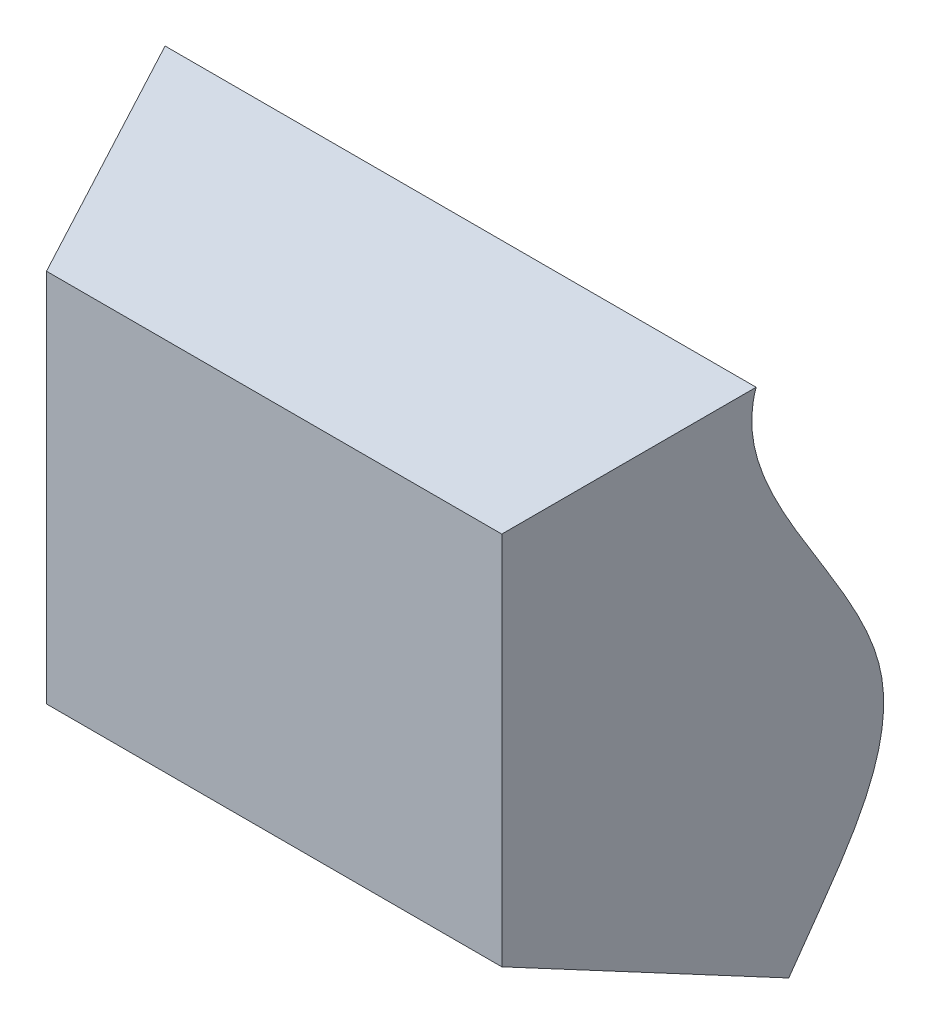
SolidWorks part; units mm, degrees
ref_plane "Спереди" through (0, 0, 0) normal (0, 0, 1) x (1, 0, 0)
ref_plane "Сверху" through (0, 0, 0) normal (0, 1, 0) x (1, 0, 0)
ref_plane "Справа" through (0, 0, 0) normal (1, 0, 0) x (0, 0, -1)
sketch "Эскиз1_fr" plane through (0, 0, 0) normal (0, 0, 1) x (1, 0, 0)
  line L1 (0, 0) -> (43.3507, 0)
  line L2 (0, 0) -> (0, -38.2597)
  line L3 (0, -38.2597) -> (43.3507, -38.2597)
  line L4 (43.3507, 0) -> (43.3507, -38.2597)
extrude "Бобышка-Вытянуть1" add sketch "Эскиз1_fr" along normal blind 20 draft 20
sketch "Эскиз1_rt" plane through (0, 0, 0) normal (1, 0, 0) x (0, 0, -1)
  spline S0 degree 3 poles (-24.0617, 6.19) (-36.3175, -2.5174) (-13.7833, -17.8971) (-31.3159, -35.3189) (-30.545, -44.4497) knots 0 0 0 0 0.484609 1 1 1 1
surface "Поверхность-Вытянуть2" sketch "Эскиз1_rt" parameters "D1"=50, "D2"=10
move or copy body "Тело-Переместить/Копировать1" bodies to move or copy 105 copy yes number of copies 1 translate (-1.5242, -2.1768, -21.3994)
other "Сечение1"
